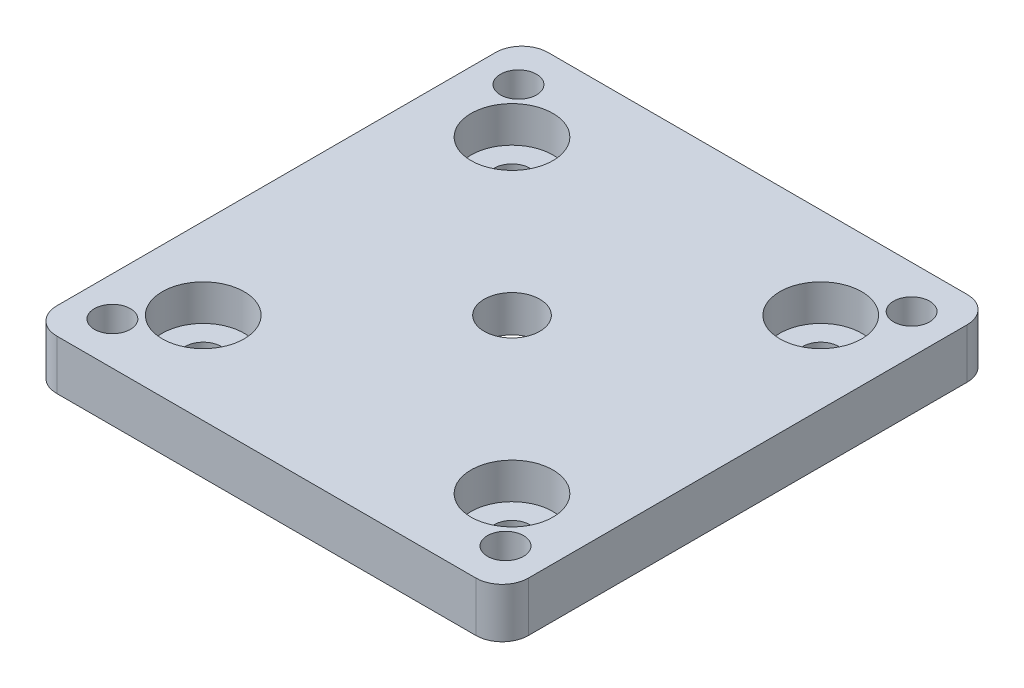
SolidWorks part; units mm, degrees
ref_plane "Front Plane" through (0, 0, 0) normal (0, 0, 1) x (1, 0, 0)
ref_plane "Top Plane" through (0, 0, 0) normal (0, 1, 0) x (1, 0, 0)
ref_plane "Right Plane" through (0, 0, 0) normal (1, 0, 0) x (0, 0, -1)
sketch "Sketch1" plane through (0, 0, 0) normal (0, 1, 0) x (1, 0, 0)
  line L0 (0, 0) -> (60.02, 0)
  line L1 (0, 0) -> (0, -62)
  line L2 (0, -62) -> (60.02, -62)
  line L3 (60.02, -62) -> (60.02, 0)
  line L5 (6.44, -7.43) -> (53.58, -7.43)
  line L6 (6.44, -7.43) -> (6.44, -54.57)
  line L7 (6.44, -54.57) -> (53.58, -54.57)
  line L8 (53.58, -7.43) -> (53.58, -54.57)
  line L9 (-5.99, 6.5) -> (66.01, 6.5)
  line L10 (-5.99, 6.5) -> (-5.99, -68.5)
  line L11 (-5.99, -68.5) -> (66.01, -68.5)
  line L12 (66.01, 6.5) -> (66.01, -68.5)
  circle A0 centre (6.44, -7.43) radius 2.75
  circle A1 centre (53.58, -7.43) radius 2.75
  circle A2 centre (53.58, -54.57) radius 2.75
  circle A3 centre (6.44, -54.57) radius 2.75
  circle A4 centre (0, 0) radius 2.75
  circle A5 centre (60.02, 0) radius 2.75
  circle A6 centre (60.02, -62) radius 2.75
  circle A7 centre (0, -62) radius 2.75
  circle A8 centre (30.01, -31) radius 4.25
  dimension "D7" = 75
  dimension "D1" = 47.14
  dimension "D2" = 60.02
  dimension "D3" = 6.44
  dimension "D4" = 47.14
  dimension "D5" = 7.43
  dimension "D6" = 62
  dimension "D8" = 72
  dimension "D9" = 5.99
  dimension "D10" = 6.5
extrude "Boss-Extrude3" add sketch "Sketch1" along normal blind 7.6 contours A3 L7 A2 L8 A1 L5 A0 L6 | A7 L2 A6 L3 A5 L0 A4 L1 A3 L6 A0 L5 A1 L8 A2 L7 | L12 L9 L10 L11 A7 L1 A4 L0 A5 L3 A6 L2 region at (30.01, 0, 0.8629) region at (30.01, 0, 8.0967) region at (30.01, 0, -5.4603)
sketch "Sketch3" plane through (0, 7.6, 0) normal (0, 1, 0) x (1, 0, 0)
  circle A0 centre (6.44, -7.43) radius 6.25
  circle A1 centre (53.58, -7.43) radius 6.25
  circle A2 centre (53.58, -54.57) radius 6.25
  circle A3 centre (6.44, -54.57) radius 6.25
extrude "Cut-Extrude1" cut sketch "Sketch3" against normal blind 5.5
fillet "Fillet1" radius 4 4 edges at (-5.99, 3.8, 68.5) (66.01, 3.8, 68.5) (66.01, 3.8, -6.5) (-5.99, 3.8, -6.5)
sketch "Sketch4" plane through (0, 0, 0) normal (0, -1, 0) x (1, 0, 0)
  circle A0 centre (30.01, 31) radius 19.3
extrude "Cut-Extrude2" cut sketch "Sketch4" against normal blind 2
